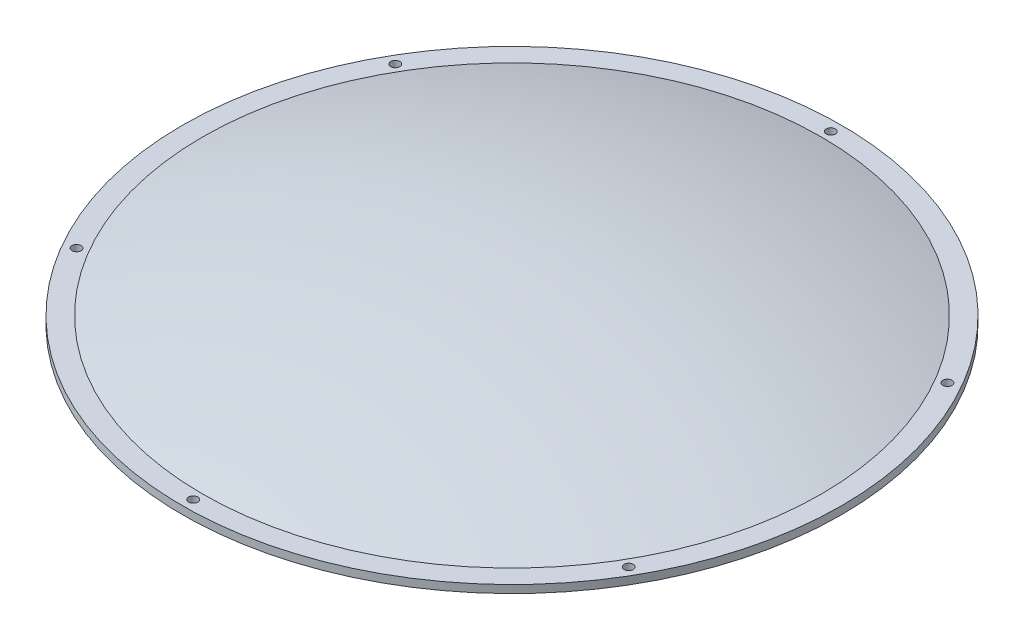
SolidWorks part; units mm, degrees
material "6061-T6 (SS)"
ref_plane "Front Plane" through (0, 0, 0) normal (0, 0, 1) x (1, 0, 0)
ref_plane "Top Plane" through (0, 0, 0) normal (0, 1, 0) x (1, 0, 0)
ref_plane "Right Plane" through (0, 0, 0) normal (1, 0, 0) x (0, 0, -1)
sketch "Sketch1" plane through (0, 0, 0) normal (0, 0, 1) x (1, 0, 0)
  line L0 (-107.3799, 282.8427) -> (107.3799, 282.8427)
  line L1 (0, 282.8427) -> (0, 102.1032)
  line L2 (0, 302.54) -> (0, 300)
  line L3 (100, 282.8427) -> (107, 282.8427)
  line L4 (0, 300) -> (-94.3927, 300) construction
  line L5 (100.4348, 285.3827) -> (107, 285.3827)
  line L6 (107, 282.8427) -> (107, 285.3827)
  line L7 (-100, 282.8427) -> (0, 0) construction
  line L8 (0, 0) -> (100, 282.8427) construction
  arc A0 (107.3799, 282.8427) -> (-107.3799, 282.8427) centre (0, 0) ccw
  arc A1 (100, 282.8427) -> (-100, 282.8427) centre (0, 0) ccw
  circle A2 centre (0, 0) radius 300 construction
  circle A3 centre (0, 0) radius 302.54 construction
  circle A4 centre (0, 0) radius 300 construction
  point P1 (149, 0)
  point P5 (0, 302.54)
  point P8 (143.4457, 43.8558)
  dimension "D1" = 300
  dimension "D2" = 200
  dimension "D4" = 2.54
  dimension "D5" = 107
  dimension "D3" = 2.54
revolve "Revolve1" add sketch "Sketch1" angle 360 about L1 region at (50.7617, 297.1474, 0) region at (104.8248, 284.5888, 0)
sketch "Sketch4" plane through (0, 282.8427, 0) normal (0, -1, 0) x (1, 0, 0)
  circle A0 centre (0, 0) radius 103.5 construction
  circle A1 centre (0, 103.5) radius 1.4732
  circle A2 centre (89.6336, 51.75) radius 1.4732
  circle A3 centre (89.6336, -51.75) radius 1.4732
  circle A4 centre (0, -103.5) radius 1.4732
  circle A5 centre (-89.6336, -51.75) radius 1.4732
  circle A6 centre (-89.6336, 51.75) radius 1.4732
  dimension "D1" = 207
  dimension "D2" = 2.9464
  dimension "D3" = 6
extrude "Cut-Extrude1" cut sketch "Sketch4" against normal through all
ref_plane "Plane1" through (0, 152, 0) normal (0, 1, 0) x (-1, 0, 0)
sketch "Sketch5" plane through (0, 152, 0) normal (0, 1, 0) x (-1, 0, 0)
  line L0 (0.866, 0) -> (2.4628, 0) construction
  line L1 (0.433, -0.75) -> (0.866, 0)
  line L2 (0.866, 0) -> (0.433, 0.75)
  line L3 (0.433, 0.75) -> (-0.433, 0.75)
  line L4 (-0.433, 0.75) -> (-0.866, 0)
  line L5 (-0.866, 0) -> (-0.433, -0.75)
  line L6 (-0.433, -0.75) -> (0.433, -0.75)
  line L7 (2.557, -0.75) -> (3.423, -0.75)
  line L8 (2.363, 0.8643) -> (1.93, 1.6143)
  line L9 (1.93, 1.6143) -> (1.064, 1.6143)
  line L10 (1.064, 1.6143) -> (0.631, 0.8643)
  line L11 (0.631, 0.8643) -> (1.064, 0.1143)
  line L12 (1.064, 0.1143) -> (1.93, 0.1143)
  line L13 (1.93, 0.1143) -> (2.363, 0.8643)
  line L14 (2.124, 0) -> (2.557, -0.75)
  line L15 (2.557, 0.75) -> (2.124, 0)
  line L16 (3.423, 0.75) -> (2.557, 0.75)
  line L17 (3.856, 0) -> (3.423, 0.75)
  line L18 (3.423, -0.75) -> (3.856, 0)
  line L19 (3.621, 0.8643) -> (4.054, 0.1143)
  line L20 (4.054, 1.6143) -> (3.621, 0.8643)
  line L21 (4.92, 1.6143) -> (4.054, 1.6143)
  line L22 (5.353, 0.8643) -> (4.92, 1.6143)
  line L23 (4.92, 0.1143) -> (5.353, 0.8643)
  line L24 (4.054, 0.1143) -> (4.92, 0.1143)
  line L25 (5.547, -0.75) -> (6.413, -0.75)
  line L26 (5.114, 0) -> (5.547, -0.75)
  line L27 (5.547, 0.75) -> (5.114, 0)
  line L28 (6.413, 0.75) -> (5.547, 0.75)
  line L29 (6.846, 0) -> (6.413, 0.75)
  line L30 (6.413, -0.75) -> (6.846, 0)
  line L31 (6.611, 0.8643) -> (7.044, 0.1143)
  line L32 (7.044, 1.6143) -> (6.611, 0.8643)
  line L33 (7.91, 1.6143) -> (7.044, 1.6143)
  line L34 (8.343, 0.8643) -> (7.91, 1.6143)
  line L35 (7.91, 0.1143) -> (8.343, 0.8643)
  line L36 (7.044, 0.1143) -> (7.91, 0.1143)
  line L37 (8.537, -0.75) -> (9.403, -0.75)
  line L38 (8.104, 0) -> (8.537, -0.75)
  line L39 (8.537, 0.75) -> (8.104, 0)
  line L40 (9.403, 0.75) -> (8.537, 0.75)
  line L41 (9.836, 0) -> (9.403, 0.75)
  line L42 (9.403, -0.75) -> (9.836, 0)
  line L43 (9.601, 0.8643) -> (10.034, 0.1143)
  line L44 (10.034, 1.6143) -> (9.601, 0.8643)
  line L45 (10.9, 1.6143) -> (10.034, 1.6143)
  line L46 (11.333, 0.8643) -> (10.9, 1.6143)
  line L47 (10.9, 0.1143) -> (11.333, 0.8643)
  line L48 (10.034, 0.1143) -> (10.9, 0.1143)
  line L49 (11.527, -0.75) -> (12.393, -0.75)
  line L50 (11.094, 0) -> (11.527, -0.75)
  line L51 (11.527, 0.75) -> (11.094, 0)
  line L52 (12.393, 0.75) -> (11.527, 0.75)
  line L53 (12.826, 0) -> (12.393, 0.75)
  line L54 (12.393, -0.75) -> (12.826, 0)
  line L55 (12.591, 0.8643) -> (13.024, 0.1143)
  line L56 (13.024, 1.6143) -> (12.591, 0.8643)
  line L57 (13.89, 1.6143) -> (13.024, 1.6143)
  line L58 (14.323, 0.8643) -> (13.89, 1.6143)
  line L59 (13.89, 0.1143) -> (14.323, 0.8643)
  line L60 (13.024, 0.1143) -> (13.89, 0.1143)
  line L61 (14.517, -0.75) -> (15.383, -0.75)
  line L62 (14.084, 0) -> (14.517, -0.75)
  line L63 (14.517, 0.75) -> (14.084, 0)
  line L64 (15.383, 0.75) -> (14.517, 0.75)
  line L65 (15.816, 0) -> (15.383, 0.75)
  line L66 (15.383, -0.75) -> (15.816, 0)
  line L67 (15.581, 0.8643) -> (16.014, 0.1143)
  line L68 (16.014, 1.6143) -> (15.581, 0.8643)
  line L69 (16.88, 1.6143) -> (16.014, 1.6143)
  line L70 (17.313, 0.8643) -> (16.88, 1.6143)
  line L71 (16.88, 0.1143) -> (17.313, 0.8643)
  line L72 (16.014, 0.1143) -> (16.88, 0.1143)
  line L73 (17.507, -0.75) -> (18.373, -0.75)
  line L74 (17.074, 0) -> (17.507, -0.75)
  line L75 (17.507, 0.75) -> (17.074, 0)
  line L76 (18.373, 0.75) -> (17.507, 0.75)
  line L77 (18.806, 0) -> (18.373, 0.75)
  line L78 (18.373, -0.75) -> (18.806, 0)
  line L79 (18.571, 0.8643) -> (19.004, 0.1143)
  line L80 (19.004, 1.6143) -> (18.571, 0.8643)
  line L81 (19.87, 1.6143) -> (19.004, 1.6143)
  line L82 (20.303, 0.8643) -> (19.87, 1.6143)
  line L83 (19.87, 0.1143) -> (20.303, 0.8643)
  line L84 (19.004, 0.1143) -> (19.87, 0.1143)
  line L85 (20.497, -0.75) -> (21.363, -0.75)
  line L86 (20.064, 0) -> (20.497, -0.75)
  line L87 (20.497, 0.75) -> (20.064, 0)
  line L88 (21.363, 0.75) -> (20.497, 0.75)
  line L89 (21.796, 0) -> (21.363, 0.75)
  line L90 (21.363, -0.75) -> (21.796, 0)
  line L91 (21.561, 0.8643) -> (21.994, 0.1143)
  line L92 (21.994, 1.6143) -> (21.561, 0.8643)
  line L93 (22.86, 1.6143) -> (21.994, 1.6143)
  line L94 (23.293, 0.8643) -> (22.86, 1.6143)
  line L95 (22.86, 0.1143) -> (23.293, 0.8643)
  line L96 (21.994, 0.1143) -> (22.86, 0.1143)
  line L97 (23.487, -0.75) -> (24.353, -0.75)
  line L98 (23.054, 0) -> (23.487, -0.75)
  line L99 (23.487, 0.75) -> (23.054, 0)
  line L100 (24.353, 0.75) -> (23.487, 0.75)
  line L101 (24.786, 0) -> (24.353, 0.75)
  line L102 (24.353, -0.75) -> (24.786, 0)
  line L103 (24.551, 0.8643) -> (24.984, 0.1143)
  line L104 (24.984, 1.6143) -> (24.551, 0.8643)
  line L105 (25.85, 1.6143) -> (24.984, 1.6143)
  line L106 (26.283, 0.8643) -> (25.85, 1.6143)
  line L107 (25.85, 0.1143) -> (26.283, 0.8643)
  line L108 (24.984, 0.1143) -> (25.85, 0.1143)
  line L109 (26.477, -0.75) -> (27.343, -0.75)
  line L110 (26.044, 0) -> (26.477, -0.75)
  line L111 (26.477, 0.75) -> (26.044, 0)
  line L112 (27.343, 0.75) -> (26.477, 0.75)
  line L113 (27.776, 0) -> (27.343, 0.75)
  line L114 (27.343, -0.75) -> (27.776, 0)
  line L115 (27.541, 0.8643) -> (27.974, 0.1143)
  line L116 (27.974, 1.6143) -> (27.541, 0.8643)
  line L117 (28.84, 1.6143) -> (27.974, 1.6143)
  line L118 (29.273, 0.8643) -> (28.84, 1.6143)
  line L119 (28.84, 0.1143) -> (29.273, 0.8643)
  line L120 (27.974, 0.1143) -> (28.84, 0.1143)
  line L121 (-0.433, 0.98) -> (0.433, 0.98)
  line L122 (-0.866, 1.73) -> (-0.433, 0.98)
  line L123 (-0.433, 2.48) -> (-0.866, 1.73)
  line L124 (0.433, 2.48) -> (-0.433, 2.48)
  line L125 (0.866, 1.73) -> (0.433, 2.48)
  line L126 (0.433, 0.98) -> (0.866, 1.73)
  line L127 (0.631, 2.5943) -> (1.064, 1.8443)
  line L128 (1.064, 3.3443) -> (0.631, 2.5943)
  line L129 (1.93, 3.3443) -> (1.064, 3.3443)
  line L130 (2.363, 2.5943) -> (1.93, 3.3443)
  line L131 (1.93, 1.8443) -> (2.363, 2.5943)
  line L132 (1.064, 1.8443) -> (1.93, 1.8443)
  line L133 (2.557, 0.98) -> (3.423, 0.98)
  line L134 (2.124, 1.73) -> (2.557, 0.98)
  line L135 (2.557, 2.48) -> (2.124, 1.73)
  line L136 (3.423, 2.48) -> (2.557, 2.48)
  line L137 (3.856, 1.73) -> (3.423, 2.48)
  line L138 (3.423, 0.98) -> (3.856, 1.73)
  line L139 (3.621, 2.5943) -> (4.054, 1.8443)
  line L140 (4.054, 3.3443) -> (3.621, 2.5943)
  line L141 (4.92, 3.3443) -> (4.054, 3.3443)
  line L142 (5.353, 2.5943) -> (4.92, 3.3443)
  line L143 (4.92, 1.8443) -> (5.353, 2.5943)
  line L144 (4.054, 1.8443) -> (4.92, 1.8443)
  line L145 (5.547, 0.98) -> (6.413, 0.98)
  line L146 (5.114, 1.73) -> (5.547, 0.98)
  line L147 (5.547, 2.48) -> (5.114, 1.73)
  line L148 (6.413, 2.48) -> (5.547, 2.48)
  line L149 (6.846, 1.73) -> (6.413, 2.48)
  line L150 (6.413, 0.98) -> (6.846, 1.73)
  line L151 (6.611, 2.5943) -> (7.044, 1.8443)
  line L152 (7.044, 3.3443) -> (6.611, 2.5943)
  line L153 (7.91, 3.3443) -> (7.044, 3.3443)
  line L154 (8.343, 2.5943) -> (7.91, 3.3443)
  line L155 (7.91, 1.8443) -> (8.343, 2.5943)
  line L156 (7.044, 1.8443) -> (7.91, 1.8443)
  line L157 (8.537, 0.98) -> (9.403, 0.98)
  line L158 (8.104, 1.73) -> (8.537, 0.98)
  line L159 (8.537, 2.48) -> (8.104, 1.73)
  line L160 (9.403, 2.48) -> (8.537, 2.48)
  line L161 (9.836, 1.73) -> (9.403, 2.48)
  line L162 (9.403, 0.98) -> (9.836, 1.73)
  line L163 (9.601, 2.5943) -> (10.034, 1.8443)
  line L164 (10.034, 3.3443) -> (9.601, 2.5943)
  line L165 (10.9, 3.3443) -> (10.034, 3.3443)
  line L166 (11.333, 2.5943) -> (10.9, 3.3443)
  line L167 (10.9, 1.8443) -> (11.333, 2.5943)
  line L168 (10.034, 1.8443) -> (10.9, 1.8443)
  line L169 (11.527, 0.98) -> (12.393, 0.98)
  line L170 (11.094, 1.73) -> (11.527, 0.98)
  line L171 (11.527, 2.48) -> (11.094, 1.73)
  line L172 (12.393, 2.48) -> (11.527, 2.48)
  line L173 (12.826, 1.73) -> (12.393, 2.48)
  line L174 (12.393, 0.98) -> (12.826, 1.73)
  line L175 (12.591, 2.5943) -> (13.024, 1.8443)
  line L176 (13.024, 3.3443) -> (12.591, 2.5943)
  line L177 (13.89, 3.3443) -> (13.024, 3.3443)
  line L178 (14.323, 2.5943) -> (13.89, 3.3443)
  line L179 (13.89, 1.8443) -> (14.323, 2.5943)
  line L180 (13.024, 1.8443) -> (13.89, 1.8443)
  line L181 (14.517, 0.98) -> (15.383, 0.98)
  line L182 (14.084, 1.73) -> (14.517, 0.98)
  line L183 (14.517, 2.48) -> (14.084, 1.73)
  line L184 (15.383, 2.48) -> (14.517, 2.48)
  line L185 (15.816, 1.73) -> (15.383, 2.48)
  line L186 (15.383, 0.98) -> (15.816, 1.73)
  line L187 (15.581, 2.5943) -> (16.014, 1.8443)
  line L188 (16.014, 3.3443) -> (15.581, 2.5943)
  line L189 (16.88, 3.3443) -> (16.014, 3.3443)
  line L190 (17.313, 2.5943) -> (16.88, 3.3443)
  line L191 (16.88, 1.8443) -> (17.313, 2.5943)
  line L192 (16.014, 1.8443) -> (16.88, 1.8443)
  line L193 (17.507, 0.98) -> (18.373, 0.98)
  line L194 (17.074, 1.73) -> (17.507, 0.98)
  line L195 (17.507, 2.48) -> (17.074, 1.73)
  line L196 (18.373, 2.48) -> (17.507, 2.48)
  line L197 (18.806, 1.73) -> (18.373, 2.48)
  line L198 (18.373, 0.98) -> (18.806, 1.73)
  line L199 (18.571, 2.5943) -> (19.004, 1.8443)
  line L200 (19.004, 3.3443) -> (18.571, 2.5943)
  line L201 (19.87, 3.3443) -> (19.004, 3.3443)
  line L202 (20.303, 2.5943) -> (19.87, 3.3443)
  line L203 (19.87, 1.8443) -> (20.303, 2.5943)
  line L204 (19.004, 1.8443) -> (19.87, 1.8443)
  line L205 (20.497, 0.98) -> (21.363, 0.98)
  line L206 (20.064, 1.73) -> (20.497, 0.98)
  line L207 (20.497, 2.48) -> (20.064, 1.73)
  line L208 (21.363, 2.48) -> (20.497, 2.48)
  line L209 (21.796, 1.73) -> (21.363, 2.48)
  line L210 (21.363, 0.98) -> (21.796, 1.73)
  line L211 (21.561, 2.5943) -> (21.994, 1.8443)
  line L212 (21.994, 3.3443) -> (21.561, 2.5943)
  line L213 (22.86, 3.3443) -> (21.994, 3.3443)
  line L214 (23.293, 2.5943) -> (22.86, 3.3443)
  line L215 (22.86, 1.8443) -> (23.293, 2.5943)
  line L216 (21.994, 1.8443) -> (22.86, 1.8443)
  line L217 (23.487, 0.98) -> (24.353, 0.98)
  line L218 (23.054, 1.73) -> (23.487, 0.98)
  line L219 (23.487, 2.48) -> (23.054, 1.73)
  line L220 (24.353, 2.48) -> (23.487, 2.48)
  line L221 (24.786, 1.73) -> (24.353, 2.48)
  line L222 (24.353, 0.98) -> (24.786, 1.73)
  line L223 (24.551, 2.5943) -> (24.984, 1.8443)
  line L224 (24.984, 3.3443) -> (24.551, 2.5943)
  line L225 (25.85, 3.3443) -> (24.984, 3.3443)
  line L226 (26.283, 2.5943) -> (25.85, 3.3443)
  line L227 (25.85, 1.8443) -> (26.283, 2.5943)
  line L228 (24.984, 1.8443) -> (25.85, 1.8443)
  line L229 (26.477, 0.98) -> (27.343, 0.98)
  line L230 (26.044, 1.73) -> (26.477, 0.98)
  line L231 (26.477, 2.48) -> (26.044, 1.73)
  line L232 (27.343, 2.48) -> (26.477, 2.48)
  line L233 (27.776, 1.73) -> (27.343, 2.48)
  line L234 (27.343, 0.98) -> (27.776, 1.73)
  line L235 (27.541, 2.5943) -> (27.974, 1.8443)
  line L236 (27.974, 3.3443) -> (27.541, 2.5943)
  line L237 (28.84, 3.3443) -> (27.974, 3.3443)
  line L238 (29.273, 2.5943) -> (28.84, 3.3443)
  line L239 (28.84, 1.8443) -> (29.273, 2.5943)
  line L240 (27.974, 1.8443) -> (28.84, 1.8443)
  line L241 (-0.433, 2.71) -> (0.433, 2.71)
  line L242 (-0.866, 3.46) -> (-0.433, 2.71)
  line L243 (-0.433, 4.21) -> (-0.866, 3.46)
  line L244 (0.433, 4.21) -> (-0.433, 4.21)
  line L245 (0.866, 3.46) -> (0.433, 4.21)
  line L246 (0.433, 2.71) -> (0.866, 3.46)
  line L247 (0.631, 4.3243) -> (1.064, 3.5743)
  line L248 (1.064, 5.0743) -> (0.631, 4.3243)
  line L249 (1.93, 5.0743) -> (1.064, 5.0743)
  line L250 (2.363, 4.3243) -> (1.93, 5.0743)
  line L251 (1.93, 3.5743) -> (2.363, 4.3243)
  line L252 (1.064, 3.5743) -> (1.93, 3.5743)
  line L253 (2.557, 2.71) -> (3.423, 2.71)
  line L254 (2.124, 3.46) -> (2.557, 2.71)
  line L255 (2.557, 4.21) -> (2.124, 3.46)
  line L256 (3.423, 4.21) -> (2.557, 4.21)
  line L257 (3.856, 3.46) -> (3.423, 4.21)
  line L258 (3.423, 2.71) -> (3.856, 3.46)
  line L259 (3.621, 4.3243) -> (4.054, 3.5743)
  line L260 (4.054, 5.0743) -> (3.621, 4.3243)
  line L261 (4.92, 5.0743) -> (4.054, 5.0743)
  line L262 (5.353, 4.3243) -> (4.92, 5.0743)
  line L263 (4.92, 3.5743) -> (5.353, 4.3243)
  line L264 (4.054, 3.5743) -> (4.92, 3.5743)
  line L265 (5.547, 2.71) -> (6.413, 2.71)
  line L266 (5.114, 3.46) -> (5.547, 2.71)
  line L267 (5.547, 4.21) -> (5.114, 3.46)
  line L268 (6.413, 4.21) -> (5.547, 4.21)
  line L269 (6.846, 3.46) -> (6.413, 4.21)
  line L270 (6.413, 2.71) -> (6.846, 3.46)
  line L271 (6.611, 4.3243) -> (7.044, 3.5743)
  line L272 (7.044, 5.0743) -> (6.611, 4.3243)
  line L273 (7.91, 5.0743) -> (7.044, 5.0743)
  line L274 (8.343, 4.3243) -> (7.91, 5.0743)
  line L275 (7.91, 3.5743) -> (8.343, 4.3243)
  line L276 (7.044, 3.5743) -> (7.91, 3.5743)
  line L277 (8.537, 2.71) -> (9.403, 2.71)
  line L278 (8.104, 3.46) -> (8.537, 2.71)
  line L279 (8.537, 4.21) -> (8.104, 3.46)
  line L280 (9.403, 4.21) -> (8.537, 4.21)
  line L281 (9.836, 3.46) -> (9.403, 4.21)
  line L282 (9.403, 2.71) -> (9.836, 3.46)
  line L283 (9.601, 4.3243) -> (10.034, 3.5743)
  line L284 (10.034, 5.0743) -> (9.601, 4.3243)
  line L285 (10.9, 5.0743) -> (10.034, 5.0743)
  line L286 (11.333, 4.3243) -> (10.9, 5.0743)
  line L287 (10.9, 3.5743) -> (11.333, 4.3243)
  line L288 (10.034, 3.5743) -> (10.9, 3.5743)
  line L289 (11.527, 2.71) -> (12.393, 2.71)
  line L290 (11.094, 3.46) -> (11.527, 2.71)
  line L291 (11.527, 4.21) -> (11.094, 3.46)
  line L292 (12.393, 4.21) -> (11.527, 4.21)
  line L293 (12.826, 3.46) -> (12.393, 4.21)
  line L294 (12.393, 2.71) -> (12.826, 3.46)
  line L295 (12.591, 4.3243) -> (13.024, 3.5743)
  line L296 (13.024, 5.0743) -> (12.591, 4.3243)
  line L297 (13.89, 5.0743) -> (13.024, 5.0743)
  line L298 (14.323, 4.3243) -> (13.89, 5.0743)
  line L299 (13.89, 3.5743) -> (14.323, 4.3243)
  line L300 (13.024, 3.5743) -> (13.89, 3.5743)
  line L301 (14.517, 2.71) -> (15.383, 2.71)
  line L302 (14.084, 3.46) -> (14.517, 2.71)
  line L303 (14.517, 4.21) -> (14.084, 3.46)
  line L304 (15.383, 4.21) -> (14.517, 4.21)
  line L305 (15.816, 3.46) -> (15.383, 4.21)
  line L306 (15.383, 2.71) -> (15.816, 3.46)
  line L307 (15.581, 4.3243) -> (16.014, 3.5743)
  line L308 (16.014, 5.0743) -> (15.581, 4.3243)
  line L309 (16.88, 5.0743) -> (16.014, 5.0743)
  line L310 (17.313, 4.3243) -> (16.88, 5.0743)
  line L311 (16.88, 3.5743) -> (17.313, 4.3243)
  line L312 (16.014, 3.5743) -> (16.88, 3.5743)
  line L313 (17.507, 2.71) -> (18.373, 2.71)
  line L314 (17.074, 3.46) -> (17.507, 2.71)
  line L315 (17.507, 4.21) -> (17.074, 3.46)
  line L316 (18.373, 4.21) -> (17.507, 4.21)
  line L317 (18.806, 3.46) -> (18.373, 4.21)
  line L318 (18.373, 2.71) -> (18.806, 3.46)
  line L319 (18.571, 4.3243) -> (19.004, 3.5743)
  line L320 (19.004, 5.0743) -> (18.571, 4.3243)
  line L321 (19.87, 5.0743) -> (19.004, 5.0743)
  line L322 (20.303, 4.3243) -> (19.87, 5.0743)
  line L323 (19.87, 3.5743) -> (20.303, 4.3243)
  line L324 (19.004, 3.5743) -> (19.87, 3.5743)
  line L325 (20.497, 2.71) -> (21.363, 2.71)
  line L326 (20.064, 3.46) -> (20.497, 2.71)
  line L327 (20.497, 4.21) -> (20.064, 3.46)
  line L328 (21.363, 4.21) -> (20.497, 4.21)
  line L329 (21.796, 3.46) -> (21.363, 4.21)
  line L330 (21.363, 2.71) -> (21.796, 3.46)
  line L331 (21.561, 4.3243) -> (21.994, 3.5743)
  line L332 (21.994, 5.0743) -> (21.561, 4.3243)
  line L333 (22.86, 5.0743) -> (21.994, 5.0743)
  line L334 (23.293, 4.3243) -> (22.86, 5.0743)
  line L335 (22.86, 3.5743) -> (23.293, 4.3243)
  line L336 (21.994, 3.5743) -> (22.86, 3.5743)
  line L337 (23.487, 2.71) -> (24.353, 2.71)
  line L338 (23.054, 3.46) -> (23.487, 2.71)
  line L339 (23.487, 4.21) -> (23.054, 3.46)
  line L340 (24.353, 4.21) -> (23.487, 4.21)
  line L341 (24.786, 3.46) -> (24.353, 4.21)
  line L342 (24.353, 2.71) -> (24.786, 3.46)
  line L343 (24.551, 4.3243) -> (24.984, 3.5743)
  line L344 (24.984, 5.0743) -> (24.551, 4.3243)
  line L345 (25.85, 5.0743) -> (24.984, 5.0743)
  line L346 (26.283, 4.3243) -> (25.85, 5.0743)
  line L347 (25.85, 3.5743) -> (26.283, 4.3243)
  line L348 (24.984, 3.5743) -> (25.85, 3.5743)
  line L349 (26.477, 2.71) -> (27.343, 2.71)
  line L350 (26.044, 3.46) -> (26.477, 2.71)
  line L351 (26.477, 4.21) -> (26.044, 3.46)
  line L352 (27.343, 4.21) -> (26.477, 4.21)
  line L353 (27.776, 3.46) -> (27.343, 4.21)
  line L354 (27.343, 2.71) -> (27.776, 3.46)
  line L355 (27.541, 4.3243) -> (27.974, 3.5743)
  line L356 (27.974, 5.0743) -> (27.541, 4.3243)
  line L357 (28.84, 5.0743) -> (27.974, 5.0743)
  line L358 (29.273, 4.3243) -> (28.84, 5.0743)
  line L359 (28.84, 3.5743) -> (29.273, 4.3243)
  line L360 (27.974, 3.5743) -> (28.84, 3.5743)
  line L361 (-0.433, 4.44) -> (0.433, 4.44)
  line L362 (-0.866, 5.19) -> (-0.433, 4.44)
  line L363 (-0.433, 5.94) -> (-0.866, 5.19)
  line L364 (0.433, 5.94) -> (-0.433, 5.94)
  line L365 (0.866, 5.19) -> (0.433, 5.94)
  line L366 (0.433, 4.44) -> (0.866, 5.19)
  line L367 (0.631, 6.0543) -> (1.064, 5.3043)
  line L368 (1.064, 6.8043) -> (0.631, 6.0543)
  line L369 (1.93, 6.8043) -> (1.064, 6.8043)
  line L370 (2.363, 6.0543) -> (1.93, 6.8043)
  line L371 (1.93, 5.3043) -> (2.363, 6.0543)
  line L372 (1.064, 5.3043) -> (1.93, 5.3043)
  line L373 (2.557, 4.44) -> (3.423, 4.44)
  line L374 (2.124, 5.19) -> (2.557, 4.44)
  line L375 (2.557, 5.94) -> (2.124, 5.19)
  line L376 (3.423, 5.94) -> (2.557, 5.94)
  line L377 (3.856, 5.19) -> (3.423, 5.94)
  line L378 (3.423, 4.44) -> (3.856, 5.19)
  line L379 (3.621, 6.0543) -> (4.054, 5.3043)
  line L380 (4.054, 6.8043) -> (3.621, 6.0543)
  line L381 (4.92, 6.8043) -> (4.054, 6.8043)
  line L382 (5.353, 6.0543) -> (4.92, 6.8043)
  line L383 (4.92, 5.3043) -> (5.353, 6.0543)
  line L384 (4.054, 5.3043) -> (4.92, 5.3043)
  line L385 (5.547, 4.44) -> (6.413, 4.44)
  line L386 (5.114, 5.19) -> (5.547, 4.44)
  line L387 (5.547, 5.94) -> (5.114, 5.19)
  line L388 (6.413, 5.94) -> (5.547, 5.94)
  line L389 (6.846, 5.19) -> (6.413, 5.94)
  line L390 (6.413, 4.44) -> (6.846, 5.19)
  line L391 (6.611, 6.0543) -> (7.044, 5.3043)
  line L392 (7.044, 6.8043) -> (6.611, 6.0543)
  line L393 (7.91, 6.8043) -> (7.044, 6.8043)
  line L394 (8.343, 6.0543) -> (7.91, 6.8043)
  line L395 (7.91, 5.3043) -> (8.343, 6.0543)
  line L396 (7.044, 5.3043) -> (7.91, 5.3043)
  line L397 (8.537, 4.44) -> (9.403, 4.44)
  line L398 (8.104, 5.19) -> (8.537, 4.44)
  line L399 (8.537, 5.94) -> (8.104, 5.19)
  line L400 (9.403, 5.94) -> (8.537, 5.94)
  line L401 (9.836, 5.19) -> (9.403, 5.94)
  line L402 (9.403, 4.44) -> (9.836, 5.19)
  line L403 (9.601, 6.0543) -> (10.034, 5.3043)
  line L404 (10.034, 6.8043) -> (9.601, 6.0543)
  line L405 (10.9, 6.8043) -> (10.034, 6.8043)
  line L406 (11.333, 6.0543) -> (10.9, 6.8043)
  line L407 (10.9, 5.3043) -> (11.333, 6.0543)
  line L408 (10.034, 5.3043) -> (10.9, 5.3043)
  line L409 (11.527, 4.44) -> (12.393, 4.44)
  line L410 (11.094, 5.19) -> (11.527, 4.44)
  line L411 (11.527, 5.94) -> (11.094, 5.19)
  line L412 (12.393, 5.94) -> (11.527, 5.94)
  line L413 (12.826, 5.19) -> (12.393, 5.94)
  line L414 (12.393, 4.44) -> (12.826, 5.19)
  line L415 (12.591, 6.0543) -> (13.024, 5.3043)
  line L416 (13.024, 6.8043) -> (12.591, 6.0543)
  line L417 (13.89, 6.8043) -> (13.024, 6.8043)
  line L418 (14.323, 6.0543) -> (13.89, 6.8043)
  line L419 (13.89, 5.3043) -> (14.323, 6.0543)
  line L420 (13.024, 5.3043) -> (13.89, 5.3043)
  line L421 (14.517, 4.44) -> (15.383, 4.44)
  line L422 (14.084, 5.19) -> (14.517, 4.44)
  line L423 (14.517, 5.94) -> (14.084, 5.19)
  line L424 (15.383, 5.94) -> (14.517, 5.94)
  line L425 (15.816, 5.19) -> (15.383, 5.94)
  line L426 (15.383, 4.44) -> (15.816, 5.19)
  line L427 (15.581, 6.0543) -> (16.014, 5.3043)
  line L428 (16.014, 6.8043) -> (15.581, 6.0543)
  line L429 (16.88, 6.8043) -> (16.014, 6.8043)
  line L430 (17.313, 6.0543) -> (16.88, 6.8043)
  line L431 (16.88, 5.3043) -> (17.313, 6.0543)
  line L432 (16.014, 5.3043) -> (16.88, 5.3043)
  line L433 (17.507, 4.44) -> (18.373, 4.44)
  line L434 (17.074, 5.19) -> (17.507, 4.44)
  line L435 (17.507, 5.94) -> (17.074, 5.19)
  line L436 (18.373, 5.94) -> (17.507, 5.94)
  line L437 (18.806, 5.19) -> (18.373, 5.94)
  line L438 (18.373, 4.44) -> (18.806, 5.19)
  line L439 (18.571, 6.0543) -> (19.004, 5.3043)
  line L440 (19.004, 6.8043) -> (18.571, 6.0543)
  line L441 (19.87, 6.8043) -> (19.004, 6.8043)
  line L442 (20.303, 6.0543) -> (19.87, 6.8043)
  line L443 (19.87, 5.3043) -> (20.303, 6.0543)
  line L444 (19.004, 5.3043) -> (19.87, 5.3043)
  line L445 (20.497, 4.44) -> (21.363, 4.44)
  line L446 (20.064, 5.19) -> (20.497, 4.44)
  line L447 (20.497, 5.94) -> (20.064, 5.19)
  line L448 (21.363, 5.94) -> (20.497, 5.94)
  line L449 (21.796, 5.19) -> (21.363, 5.94)
  line L450 (21.363, 4.44) -> (21.796, 5.19)
  line L451 (21.561, 6.0543) -> (21.994, 5.3043)
  line L452 (21.994, 6.8043) -> (21.561, 6.0543)
  line L453 (22.86, 6.8043) -> (21.994, 6.8043)
  line L454 (23.293, 6.0543) -> (22.86, 6.8043)
  line L455 (22.86, 5.3043) -> (23.293, 6.0543)
  line L456 (21.994, 5.3043) -> (22.86, 5.3043)
  line L457 (23.487, 4.44) -> (24.353, 4.44)
  line L458 (23.054, 5.19) -> (23.487, 4.44)
  line L459 (23.487, 5.94) -> (23.054, 5.19)
  line L460 (24.353, 5.94) -> (23.487, 5.94)
  line L461 (24.786, 5.19) -> (24.353, 5.94)
  line L462 (24.353, 4.44) -> (24.786, 5.19)
  line L463 (24.551, 6.0543) -> (24.984, 5.3043)
  line L464 (24.984, 6.8043) -> (24.551, 6.0543)
  line L465 (25.85, 6.8043) -> (24.984, 6.8043)
  line L466 (26.283, 6.0543) -> (25.85, 6.8043)
  line L467 (25.85, 5.3043) -> (26.283, 6.0543)
  line L468 (24.984, 5.3043) -> (25.85, 5.3043)
  line L469 (26.477, 4.44) -> (27.343, 4.44)
  line L470 (26.044, 5.19) -> (26.477, 4.44)
  line L471 (26.477, 5.94) -> (26.044, 5.19)
  line L472 (27.343, 5.94) -> (26.477, 5.94)
  line L473 (27.776, 5.19) -> (27.343, 5.94)
  line L474 (27.343, 4.44) -> (27.776, 5.19)
  line L475 (27.541, 6.0543) -> (27.974, 5.3043)
  line L476 (27.974, 6.8043) -> (27.541, 6.0543)
  line L477 (28.84, 6.8043) -> (27.974, 6.8043)
  line L478 (29.273, 6.0543) -> (28.84, 6.8043)
  line L479 (28.84, 5.3043) -> (29.273, 6.0543)
  line L480 (27.974, 5.3043) -> (28.84, 5.3043)
  line L481 (-0.433, 6.17) -> (0.433, 6.17)
  line L482 (-0.866, 6.92) -> (-0.433, 6.17)
  line L483 (-0.433, 7.67) -> (-0.866, 6.92)
  line L484 (0.433, 7.67) -> (-0.433, 7.67)
  line L485 (0.866, 6.92) -> (0.433, 7.67)
  line L486 (0.433, 6.17) -> (0.866, 6.92)
  line L487 (0.631, 7.7843) -> (1.064, 7.0343)
  line L488 (1.064, 8.5343) -> (0.631, 7.7843)
  line L489 (1.93, 8.5343) -> (1.064, 8.5343)
  line L490 (2.363, 7.7843) -> (1.93, 8.5343)
  line L491 (1.93, 7.0343) -> (2.363, 7.7843)
  line L492 (1.064, 7.0343) -> (1.93, 7.0343)
  line L493 (2.557, 6.17) -> (3.423, 6.17)
  line L494 (2.124, 6.92) -> (2.557, 6.17)
  line L495 (2.557, 7.67) -> (2.124, 6.92)
  line L496 (3.423, 7.67) -> (2.557, 7.67)
  line L497 (3.856, 6.92) -> (3.423, 7.67)
  line L498 (3.423, 6.17) -> (3.856, 6.92)
  line L499 (3.621, 7.7843) -> (4.054, 7.0343)
  line L500 (4.054, 8.5343) -> (3.621, 7.7843)
  line L501 (4.92, 8.5343) -> (4.054, 8.5343)
  line L502 (5.353, 7.7843) -> (4.92, 8.5343)
  line L503 (4.92, 7.0343) -> (5.353, 7.7843)
  line L504 (4.054, 7.0343) -> (4.92, 7.0343)
  line L505 (5.547, 6.17) -> (6.413, 6.17)
  line L506 (5.114, 6.92) -> (5.547, 6.17)
  line L507 (5.547, 7.67) -> (5.114, 6.92)
  line L508 (6.413, 7.67) -> (5.547, 7.67)
  line L509 (6.846, 6.92) -> (6.413, 7.67)
  line L510 (6.413, 6.17) -> (6.846, 6.92)
  line L511 (6.611, 7.7843) -> (7.044, 7.0343)
  line L512 (7.044, 8.5343) -> (6.611, 7.7843)
  line L513 (7.91, 8.5343) -> (7.044, 8.5343)
  line L514 (8.343, 7.7843) -> (7.91, 8.5343)
  line L515 (7.91, 7.0343) -> (8.343, 7.7843)
  line L516 (7.044, 7.0343) -> (7.91, 7.0343)
  line L517 (8.537, 6.17) -> (9.403, 6.17)
  line L518 (8.104, 6.92) -> (8.537, 6.17)
  line L519 (8.537, 7.67) -> (8.104, 6.92)
  line L520 (9.403, 7.67) -> (8.537, 7.67)
  line L521 (9.836, 6.92) -> (9.403, 7.67)
  line L522 (9.403, 6.17) -> (9.836, 6.92)
  line L523 (9.601, 7.7843) -> (10.034, 7.0343)
  line L524 (10.034, 8.5343) -> (9.601, 7.7843)
  line L525 (10.9, 8.5343) -> (10.034, 8.5343)
  line L526 (11.333, 7.7843) -> (10.9, 8.5343)
  line L527 (10.9, 7.0343) -> (11.333, 7.7843)
  line L528 (10.034, 7.0343) -> (10.9, 7.0343)
  line L529 (11.527, 6.17) -> (12.393, 6.17)
  line L530 (11.094, 6.92) -> (11.527, 6.17)
  line L531 (11.527, 7.67) -> (11.094, 6.92)
  line L532 (12.393, 7.67) -> (11.527, 7.67)
  line L533 (12.826, 6.92) -> (12.393, 7.67)
  line L534 (12.393, 6.17) -> (12.826, 6.92)
  line L535 (12.591, 7.7843) -> (13.024, 7.0343)
  line L536 (13.024, 8.5343) -> (12.591, 7.7843)
  line L537 (13.89, 8.5343) -> (13.024, 8.5343)
  line L538 (14.323, 7.7843) -> (13.89, 8.5343)
  line L539 (13.89, 7.0343) -> (14.323, 7.7843)
  line L540 (13.024, 7.0343) -> (13.89, 7.0343)
  line L541 (14.517, 6.17) -> (15.383, 6.17)
  line L542 (14.084, 6.92) -> (14.517, 6.17)
  line L543 (14.517, 7.67) -> (14.084, 6.92)
  line L544 (15.383, 7.67) -> (14.517, 7.67)
  line L545 (15.816, 6.92) -> (15.383, 7.67)
  line L546 (15.383, 6.17) -> (15.816, 6.92)
  line L547 (15.581, 7.7843) -> (16.014, 7.0343)
  line L548 (16.014, 8.5343) -> (15.581, 7.7843)
  line L549 (16.88, 8.5343) -> (16.014, 8.5343)
  line L550 (17.313, 7.7843) -> (16.88, 8.5343)
  line L551 (16.88, 7.0343) -> (17.313, 7.7843)
  line L552 (16.014, 7.0343) -> (16.88, 7.0343)
  line L553 (17.507, 6.17) -> (18.373, 6.17)
  line L554 (17.074, 6.92) -> (17.507, 6.17)
  line L555 (17.507, 7.67) -> (17.074, 6.92)
  line L556 (18.373, 7.67) -> (17.507, 7.67)
  line L557 (18.806, 6.92) -> (18.373, 7.67)
  line L558 (18.373, 6.17) -> (18.806, 6.92)
  line L559 (18.571, 7.7843) -> (19.004, 7.0343)
  line L560 (19.004, 8.5343) -> (18.571, 7.7843)
  line L561 (19.87, 8.5343) -> (19.004, 8.5343)
  line L562 (20.303, 7.7843) -> (19.87, 8.5343)
  line L563 (19.87, 7.0343) -> (20.303, 7.7843)
  line L564 (19.004, 7.0343) -> (19.87, 7.0343)
  line L565 (20.497, 6.17) -> (21.363, 6.17)
  line L566 (20.064, 6.92) -> (20.497, 6.17)
  line L567 (20.497, 7.67) -> (20.064, 6.92)
  line L568 (21.363, 7.67) -> (20.497, 7.67)
  line L569 (21.796, 6.92) -> (21.363, 7.67)
  line L570 (21.363, 6.17) -> (21.796, 6.92)
  line L571 (21.561, 7.7843) -> (21.994, 7.0343)
  line L572 (21.994, 8.5343) -> (21.561, 7.7843)
  line L573 (22.86, 8.5343) -> (21.994, 8.5343)
  line L574 (23.293, 7.7843) -> (22.86, 8.5343)
  line L575 (22.86, 7.0343) -> (23.293, 7.7843)
  line L576 (21.994, 7.0343) -> (22.86, 7.0343)
  line L577 (23.487, 6.17) -> (24.353, 6.17)
  line L578 (23.054, 6.92) -> (23.487, 6.17)
  line L579 (23.487, 7.67) -> (23.054, 6.92)
  line L580 (24.353, 7.67) -> (23.487, 7.67)
  line L581 (24.786, 6.92) -> (24.353, 7.67)
  line L582 (24.353, 6.17) -> (24.786, 6.92)
  line L583 (24.551, 7.7843) -> (24.984, 7.0343)
  line L584 (24.984, 8.5343) -> (24.551, 7.7843)
  line L585 (25.85, 8.5343) -> (24.984, 8.5343)
  line L586 (26.283, 7.7843) -> (25.85, 8.5343)
  line L587 (25.85, 7.0343) -> (26.283, 7.7843)
  line L588 (24.984, 7.0343) -> (25.85, 7.0343)
  line L589 (26.477, 6.17) -> (27.343, 6.17)
  line L590 (26.044, 6.92) -> (26.477, 6.17)
  line L591 (26.477, 7.67) -> (26.044, 6.92)
  line L592 (27.343, 7.67) -> (26.477, 7.67)
  line L593 (27.776, 6.92) -> (27.343, 7.67)
  line L594 (27.343, 6.17) -> (27.776, 6.92)
  line L595 (27.541, 7.7843) -> (27.974, 7.0343)
  line L596 (27.974, 8.5343) -> (27.541, 7.7843)
  line L597 (28.84, 8.5343) -> (27.974, 8.5343)
  line L598 (29.273, 7.7843) -> (28.84, 8.5343)
  line L599 (28.84, 7.0343) -> (29.273, 7.7843)
  line L600 (27.974, 7.0343) -> (28.84, 7.0343)
  line L601 (-0.433, 7.9) -> (0.433, 7.9)
  line L602 (-0.866, 8.65) -> (-0.433, 7.9)
  line L603 (-0.433, 9.4) -> (-0.866, 8.65)
  line L604 (0.433, 9.4) -> (-0.433, 9.4)
  line L605 (0.866, 8.65) -> (0.433, 9.4)
  line L606 (0.433, 7.9) -> (0.866, 8.65)
  line L607 (0.631, 9.5143) -> (1.064, 8.7643)
  line L608 (1.064, 10.2643) -> (0.631, 9.5143)
  line L609 (1.93, 10.2643) -> (1.064, 10.2643)
  line L610 (2.363, 9.5143) -> (1.93, 10.2643)
  line L611 (1.93, 8.7643) -> (2.363, 9.5143)
  line L612 (1.064, 8.7643) -> (1.93, 8.7643)
  line L613 (2.557, 7.9) -> (3.423, 7.9)
  line L614 (2.124, 8.65) -> (2.557, 7.9)
  line L615 (2.557, 9.4) -> (2.124, 8.65)
  line L616 (3.423, 9.4) -> (2.557, 9.4)
  line L617 (3.856, 8.65) -> (3.423, 9.4)
  line L618 (3.423, 7.9) -> (3.856, 8.65)
  line L619 (3.621, 9.5143) -> (4.054, 8.7643)
  line L620 (4.054, 10.2643) -> (3.621, 9.5143)
  line L621 (4.92, 10.2643) -> (4.054, 10.2643)
  line L622 (5.353, 9.5143) -> (4.92, 10.2643)
  line L623 (4.92, 8.7643) -> (5.353, 9.5143)
  line L624 (4.054, 8.7643) -> (4.92, 8.7643)
  line L625 (5.547, 7.9) -> (6.413, 7.9)
  line L626 (5.114, 8.65) -> (5.547, 7.9)
  line L627 (5.547, 9.4) -> (5.114, 8.65)
  line L628 (6.413, 9.4) -> (5.547, 9.4)
  line L629 (6.846, 8.65) -> (6.413, 9.4)
  line L630 (6.413, 7.9) -> (6.846, 8.65)
  line L631 (6.611, 9.5143) -> (7.044, 8.7643)
  line L632 (7.044, 10.2643) -> (6.611, 9.5143)
  line L633 (7.91, 10.2643) -> (7.044, 10.2643)
  line L634 (8.343, 9.5143) -> (7.91, 10.2643)
  line L635 (7.91, 8.7643) -> (8.343, 9.5143)
  line L636 (7.044, 8.7643) -> (7.91, 8.7643)
  line L637 (8.537, 7.9) -> (9.403, 7.9)
  line L638 (8.104, 8.65) -> (8.537, 7.9)
  line L639 (8.537, 9.4) -> (8.104, 8.65)
  line L640 (9.403, 9.4) -> (8.537, 9.4)
  line L641 (9.836, 8.65) -> (9.403, 9.4)
  line L642 (9.403, 7.9) -> (9.836, 8.65)
  line L643 (9.601, 9.5143) -> (10.034, 8.7643)
  line L644 (10.034, 10.2643) -> (9.601, 9.5143)
  line L645 (10.9, 10.2643) -> (10.034, 10.2643)
  line L646 (11.333, 9.5143) -> (10.9, 10.2643)
  line L647 (10.9, 8.7643) -> (11.333, 9.5143)
  line L648 (10.034, 8.7643) -> (10.9, 8.7643)
  line L649 (11.527, 7.9) -> (12.393, 7.9)
  line L650 (11.094, 8.65) -> (11.527, 7.9)
  line L651 (11.527, 9.4) -> (11.094, 8.65)
  line L652 (12.393, 9.4) -> (11.527, 9.4)
  line L653 (12.826, 8.65) -> (12.393, 9.4)
  line L654 (12.393, 7.9) -> (12.826, 8.65)
  line L655 (12.591, 9.5143) -> (13.024, 8.7643)
  line L656 (13.024, 10.2643) -> (12.591, 9.5143)
  line L657 (13.89, 10.2643) -> (13.024, 10.2643)
  line L658 (14.323, 9.5143) -> (13.89, 10.2643)
  line L659 (13.89, 8.7643) -> (14.323, 9.5143)
  line L660 (13.024, 8.7643) -> (13.89, 8.7643)
  line L661 (14.517, 7.9) -> (15.383, 7.9)
  line L662 (14.084, 8.65) -> (14.517, 7.9)
  line L663 (14.517, 9.4) -> (14.084, 8.65)
  line L664 (15.383, 9.4) -> (14.517, 9.4)
  line L665 (15.816, 8.65) -> (15.383, 9.4)
  line L666 (15.383, 7.9) -> (15.816, 8.65)
  line L667 (15.581, 9.5143) -> (16.014, 8.7643)
  line L668 (16.014, 10.2643) -> (15.581, 9.5143)
  line L669 (16.88, 10.2643) -> (16.014, 10.2643)
  line L670 (17.313, 9.5143) -> (16.88, 10.2643)
  line L671 (16.88, 8.7643) -> (17.313, 9.5143)
  line L672 (16.014, 8.7643) -> (16.88, 8.7643)
  line L673 (17.507, 7.9) -> (18.373, 7.9)
  line L674 (17.074, 8.65) -> (17.507, 7.9)
  line L675 (17.507, 9.4) -> (17.074, 8.65)
  line L676 (18.373, 9.4) -> (17.507, 9.4)
  line L677 (18.806, 8.65) -> (18.373, 9.4)
  line L678 (18.373, 7.9) -> (18.806, 8.65)
  line L679 (18.571, 9.5143) -> (19.004, 8.7643)
  line L680 (19.004, 10.2643) -> (18.571, 9.5143)
  line L681 (19.87, 10.2643) -> (19.004, 10.2643)
  line L682 (20.303, 9.5143) -> (19.87, 10.2643)
  line L683 (19.87, 8.7643) -> (20.303, 9.5143)
  line L684 (19.004, 8.7643) -> (19.87, 8.7643)
  line L685 (20.497, 7.9) -> (21.363, 7.9)
  line L686 (20.064, 8.65) -> (20.497, 7.9)
  line L687 (20.497, 9.4) -> (20.064, 8.65)
  line L688 (21.363, 9.4) -> (20.497, 9.4)
  line L689 (21.796, 8.65) -> (21.363, 9.4)
  line L690 (21.363, 7.9) -> (21.796, 8.65)
  line L691 (21.561, 9.5143) -> (21.994, 8.7643)
  line L692 (21.994, 10.2643) -> (21.561, 9.5143)
  line L693 (22.86, 10.2643) -> (21.994, 10.2643)
  line L694 (23.293, 9.5143) -> (22.86, 10.2643)
  line L695 (22.86, 8.7643) -> (23.293, 9.5143)
  line L696 (21.994, 8.7643) -> (22.86, 8.7643)
  line L697 (23.487, 7.9) -> (24.353, 7.9)
  line L698 (23.054, 8.65) -> (23.487, 7.9)
  line L699 (23.487, 9.4) -> (23.054, 8.65)
  line L700 (24.353, 9.4) -> (23.487, 9.4)
  line L701 (24.786, 8.65) -> (24.353, 9.4)
  line L702 (24.353, 7.9) -> (24.786, 8.65)
  line L703 (24.551, 9.5143) -> (24.984, 8.7643)
  line L704 (24.984, 10.2643) -> (24.551, 9.5143)
  line L705 (25.85, 10.2643) -> (24.984, 10.2643)
  line L706 (26.283, 9.5143) -> (25.85, 10.2643)
  line L707 (25.85, 8.7643) -> (26.283, 9.5143)
  line L708 (24.984, 8.7643) -> (25.85, 8.7643)
  line L709 (26.477, 7.9) -> (27.343, 7.9)
  line L710 (26.044, 8.65) -> (26.477, 7.9)
  line L711 (26.477, 9.4) -> (26.044, 8.65)
  line L712 (27.343, 9.4) -> (26.477, 9.4)
  line L713 (27.776, 8.65) -> (27.343, 9.4)
  line L714 (27.343, 7.9) -> (27.776, 8.65)
  line L715 (27.541, 9.5143) -> (27.974, 8.7643)
  line L716 (27.974, 10.2643) -> (27.541, 9.5143)
  line L717 (28.84, 10.2643) -> (27.974, 10.2643)
  line L718 (29.273, 9.5143) -> (28.84, 10.2643)
  line L719 (28.84, 8.7643) -> (29.273, 9.5143)
  line L720 (27.974, 8.7643) -> (28.84, 8.7643)
  line L721 (-0.433, 9.63) -> (0.433, 9.63)
  line L722 (-0.866, 10.38) -> (-0.433, 9.63)
  line L723 (-0.433, 11.13) -> (-0.866, 10.38)
  line L724 (0.433, 11.13) -> (-0.433, 11.13)
  line L725 (0.866, 10.38) -> (0.433, 11.13)
  line L726 (0.433, 9.63) -> (0.866, 10.38)
  line L727 (0.631, 11.2443) -> (1.064, 10.4943)
  line L728 (1.064, 11.9943) -> (0.631, 11.2443)
  line L729 (1.93, 11.9943) -> (1.064, 11.9943)
  line L730 (2.363, 11.2443) -> (1.93, 11.9943)
  line L731 (1.93, 10.4943) -> (2.363, 11.2443)
  line L732 (1.064, 10.4943) -> (1.93, 10.4943)
  line L733 (2.557, 9.63) -> (3.423, 9.63)
  line L734 (2.124, 10.38) -> (2.557, 9.63)
  line L735 (2.557, 11.13) -> (2.124, 10.38)
  line L736 (3.423, 11.13) -> (2.557, 11.13)
  line L737 (3.856, 10.38) -> (3.423, 11.13)
  line L738 (3.423, 9.63) -> (3.856, 10.38)
  line L739 (3.621, 11.2443) -> (4.054, 10.4943)
  line L740 (4.054, 11.9943) -> (3.621, 11.2443)
  line L741 (4.92, 11.9943) -> (4.054, 11.9943)
  line L742 (5.353, 11.2443) -> (4.92, 11.9943)
  line L743 (4.92, 10.4943) -> (5.353, 11.2443)
  line L744 (4.054, 10.4943) -> (4.92, 10.4943)
  line L745 (5.547, 9.63) -> (6.413, 9.63)
  line L746 (5.114, 10.38) -> (5.547, 9.63)
  line L747 (5.547, 11.13) -> (5.114, 10.38)
  line L748 (6.413, 11.13) -> (5.547, 11.13)
  line L749 (6.846, 10.38) -> (6.413, 11.13)
  line L750 (6.413, 9.63) -> (6.846, 10.38)
  line L751 (6.611, 11.2443) -> (7.044, 10.4943)
  line L752 (7.044, 11.9943) -> (6.611, 11.2443)
  line L753 (7.91, 11.9943) -> (7.044, 11.9943)
  line L754 (8.343, 11.2443) -> (7.91, 11.9943)
  line L755 (7.91, 10.4943) -> (8.343, 11.2443)
  line L756 (7.044, 10.4943) -> (7.91, 10.4943)
  line L757 (8.537, 9.63) -> (9.403, 9.63)
  line L758 (8.104, 10.38) -> (8.537, 9.63)
  line L759 (8.537, 11.13) -> (8.104, 10.38)
  line L760 (9.403, 11.13) -> (8.537, 11.13)
  line L761 (9.836, 10.38) -> (9.403, 11.13)
  line L762 (9.403, 9.63) -> (9.836, 10.38)
  line L763 (9.601, 11.2443) -> (10.034, 10.4943)
  line L764 (10.034, 11.9943) -> (9.601, 11.2443)
  line L765 (10.9, 11.9943) -> (10.034, 11.9943)
  line L766 (11.333, 11.2443) -> (10.9, 11.9943)
  line L767 (10.9, 10.4943) -> (11.333, 11.2443)
  line L768 (10.034, 10.4943) -> (10.9, 10.4943)
  line L769 (11.527, 9.63) -> (12.393, 9.63)
  line L770 (11.094, 10.38) -> (11.527, 9.63)
  line L771 (11.527, 11.13) -> (11.094, 10.38)
  line L772 (12.393, 11.13) -> (11.527, 11.13)
  line L773 (12.826, 10.38) -> (12.393, 11.13)
  line L774 (12.393, 9.63) -> (12.826, 10.38)
  line L775 (12.591, 11.2443) -> (13.024, 10.4943)
  line L776 (13.024, 11.9943) -> (12.591, 11.2443)
  line L777 (13.89, 11.9943) -> (13.024, 11.9943)
  line L778 (14.323, 11.2443) -> (13.89, 11.9943)
  line L779 (13.89, 10.4943) -> (14.323, 11.2443)
  line L780 (13.024, 10.4943) -> (13.89, 10.4943)
  line L781 (14.517, 9.63) -> (15.383, 9.63)
  line L782 (14.084, 10.38) -> (14.517, 9.63)
  line L783 (14.517, 11.13) -> (14.084, 10.38)
  line L784 (15.383, 11.13) -> (14.517, 11.13)
  line L785 (15.816, 10.38) -> (15.383, 11.13)
  line L786 (15.383, 9.63) -> (15.816, 10.38)
  line L787 (15.581, 11.2443) -> (16.014, 10.4943)
  line L788 (16.014, 11.9943) -> (15.581, 11.2443)
  line L789 (16.88, 11.9943) -> (16.014, 11.9943)
  line L790 (17.313, 11.2443) -> (16.88, 11.9943)
  line L791 (16.88, 10.4943) -> (17.313, 11.2443)
  line L792 (16.014, 10.4943) -> (16.88, 10.4943)
  line L793 (17.507, 9.63) -> (18.373, 9.63)
  line L794 (17.074, 10.38) -> (17.507, 9.63)
  line L795 (17.507, 11.13) -> (17.074, 10.38)
  line L796 (18.373, 11.13) -> (17.507, 11.13)
  line L797 (18.806, 10.38) -> (18.373, 11.13)
  line L798 (18.373, 9.63) -> (18.806, 10.38)
  line L799 (18.571, 11.2443) -> (19.004, 10.4943)
  line L800 (19.004, 11.9943) -> (18.571, 11.2443)
  line L801 (19.87, 11.9943) -> (19.004, 11.9943)
  line L802 (20.303, 11.2443) -> (19.87, 11.9943)
  line L803 (19.87, 10.4943) -> (20.303, 11.2443)
  line L804 (19.004, 10.4943) -> (19.87, 10.4943)
  line L805 (20.497, 9.63) -> (21.363, 9.63)
  line L806 (20.064, 10.38) -> (20.497, 9.63)
  line L807 (20.497, 11.13) -> (20.064, 10.38)
  line L808 (21.363, 11.13) -> (20.497, 11.13)
  line L809 (21.796, 10.38) -> (21.363, 11.13)
  line L810 (21.363, 9.63) -> (21.796, 10.38)
  line L811 (21.561, 11.2443) -> (21.994, 10.4943)
  line L812 (21.994, 11.9943) -> (21.561, 11.2443)
  line L813 (22.86, 11.9943) -> (21.994, 11.9943)
  line L814 (23.293, 11.2443) -> (22.86, 11.9943)
  line L815 (22.86, 10.4943) -> (23.293, 11.2443)
  line L816 (21.994, 10.4943) -> (22.86, 10.4943)
  line L817 (23.487, 9.63) -> (24.353, 9.63)
  line L818 (23.054, 10.38) -> (23.487, 9.63)
  line L819 (23.487, 11.13) -> (23.054, 10.38)
  line L820 (24.353, 11.13) -> (23.487, 11.13)
  line L821 (24.786, 10.38) -> (24.353, 11.13)
  line L822 (24.353, 9.63) -> (24.786, 10.38)
  line L823 (24.551, 11.2443) -> (24.984, 10.4943)
  line L824 (24.984, 11.9943) -> (24.551, 11.2443)
  line L825 (25.85, 11.9943) -> (24.984, 11.9943)
  line L826 (26.283, 11.2443) -> (25.85, 11.9943)
  line L827 (25.85, 10.4943) -> (26.283, 11.2443)
  line L828 (24.984, 10.4943) -> (25.85, 10.4943)
  line L829 (26.477, 9.63) -> (27.343, 9.63)
  line L830 (26.044, 10.38) -> (26.477, 9.63)
  line L831 (26.477, 11.13) -> (26.044, 10.38)
  line L832 (27.343, 11.13) -> (26.477, 11.13)
  line L833 (27.776, 10.38) -> (27.343, 11.13)
  line L834 (27.343, 9.63) -> (27.776, 10.38)
  line L835 (27.541, 11.2443) -> (27.974, 10.4943)
  line L836 (27.974, 11.9943) -> (27.541, 11.2443)
  line L837 (28.84, 11.9943) -> (27.974, 11.9943)
  line L838 (29.273, 11.2443) -> (28.84, 11.9943)
  line L839 (28.84, 10.4943) -> (29.273, 11.2443)
  line L840 (27.974, 10.4943) -> (28.84, 10.4943)
  line L841 (-0.433, 11.36) -> (0.433, 11.36)
  line L842 (-0.866, 12.11) -> (-0.433, 11.36)
  line L843 (-0.433, 12.86) -> (-0.866, 12.11)
  line L844 (0.433, 12.86) -> (-0.433, 12.86)
  line L845 (0.866, 12.11) -> (0.433, 12.86)
  line L846 (0.433, 11.36) -> (0.866, 12.11)
  line L847 (0.631, 12.9743) -> (1.064, 12.2243)
  line L848 (1.064, 13.7243) -> (0.631, 12.9743)
  line L849 (1.93, 13.7243) -> (1.064, 13.7243)
  line L850 (2.363, 12.9743) -> (1.93, 13.7243)
  line L851 (1.93, 12.2243) -> (2.363, 12.9743)
  line L852 (1.064, 12.2243) -> (1.93, 12.2243)
  line L853 (2.557, 11.36) -> (3.423, 11.36)
  line L854 (2.124, 12.11) -> (2.557, 11.36)
  line L855 (2.557, 12.86) -> (2.124, 12.11)
  line L856 (3.423, 12.86) -> (2.557, 12.86)
  line L857 (3.856, 12.11) -> (3.423, 12.86)
  line L858 (3.423, 11.36) -> (3.856, 12.11)
  line L859 (3.621, 12.9743) -> (4.054, 12.2243)
  line L860 (4.054, 13.7243) -> (3.621, 12.9743)
  line L861 (4.92, 13.7243) -> (4.054, 13.7243)
  line L862 (5.353, 12.9743) -> (4.92, 13.7243)
  line L863 (4.92, 12.2243) -> (5.353, 12.9743)
  line L864 (4.054, 12.2243) -> (4.92, 12.2243)
  line L865 (5.547, 11.36) -> (6.413, 11.36)
  line L866 (5.114, 12.11) -> (5.547, 11.36)
  line L867 (5.547, 12.86) -> (5.114, 12.11)
  line L868 (6.413, 12.86) -> (5.547, 12.86)
  line L869 (6.846, 12.11) -> (6.413, 12.86)
  line L870 (6.413, 11.36) -> (6.846, 12.11)
  line L871 (6.611, 12.9743) -> (7.044, 12.2243)
  line L872 (7.044, 13.7243) -> (6.611, 12.9743)
  line L873 (7.91, 13.7243) -> (7.044, 13.7243)
  line L874 (8.343, 12.9743) -> (7.91, 13.7243)
  line L875 (7.91, 12.2243) -> (8.343, 12.9743)
  line L876 (7.044, 12.2243) -> (7.91, 12.2243)
  line L877 (8.537, 11.36) -> (9.403, 11.36)
  line L878 (8.104, 12.11) -> (8.537, 11.36)
  line L879 (8.537, 12.86) -> (8.104, 12.11)
  line L880 (9.403, 12.86) -> (8.537, 12.86)
  line L881 (9.836, 12.11) -> (9.403, 12.86)
  line L882 (9.403, 11.36) -> (9.836, 12.11)
  line L883 (9.601, 12.9743) -> (10.034, 12.2243)
  line L884 (10.034, 13.7243) -> (9.601, 12.9743)
  line L885 (10.9, 13.7243) -> (10.034, 13.7243)
  line L886 (11.333, 12.9743) -> (10.9, 13.7243)
  line L887 (10.9, 12.2243) -> (11.333, 12.9743)
  line L888 (10.034, 12.2243) -> (10.9, 12.2243)
  line L889 (11.527, 11.36) -> (12.393, 11.36)
  line L890 (11.094, 12.11) -> (11.527, 11.36)
  line L891 (11.527, 12.86) -> (11.094, 12.11)
  line L892 (12.393, 12.86) -> (11.527, 12.86)
  line L893 (12.826, 12.11) -> (12.393, 12.86)
  line L894 (12.393, 11.36) -> (12.826, 12.11)
  line L895 (12.591, 12.9743) -> (13.024, 12.2243)
  line L896 (13.024, 13.7243) -> (12.591, 12.9743)
  line L897 (13.89, 13.7243) -> (13.024, 13.7243)
  line L898 (14.323, 12.9743) -> (13.89, 13.7243)
  line L899 (13.89, 12.2243) -> (14.323, 12.9743)
  line L900 (13.024, 12.2243) -> (13.89, 12.2243)
  line L901 (14.517, 11.36) -> (15.383, 11.36)
  line L902 (14.084, 12.11) -> (14.517, 11.36)
  line L903 (14.517, 12.86) -> (14.084, 12.11)
  line L904 (15.383, 12.86) -> (14.517, 12.86)
  line L905 (15.816, 12.11) -> (15.383, 12.86)
  line L906 (15.383, 11.36) -> (15.816, 12.11)
  line L907 (15.581, 12.9743) -> (16.014, 12.2243)
  line L908 (16.014, 13.7243) -> (15.581, 12.9743)
  line L909 (16.88, 13.7243) -> (16.014, 13.7243)
  line L910 (17.313, 12.9743) -> (16.88, 13.7243)
  line L911 (16.88, 12.2243) -> (17.313, 12.9743)
  line L912 (16.014, 12.2243) -> (16.88, 12.2243)
  line L913 (17.507, 11.36) -> (18.373, 11.36)
  line L914 (17.074, 12.11) -> (17.507, 11.36)
  line L915 (17.507, 12.86) -> (17.074, 12.11)
  line L916 (18.373, 12.86) -> (17.507, 12.86)
  line L917 (18.806, 12.11) -> (18.373, 12.86)
  line L918 (18.373, 11.36) -> (18.806, 12.11)
  line L919 (18.571, 12.9743) -> (19.004, 12.2243)
  line L920 (19.004, 13.7243) -> (18.571, 12.9743)
  line L921 (19.87, 13.7243) -> (19.004, 13.7243)
  line L922 (20.303, 12.9743) -> (19.87, 13.7243)
  line L923 (19.87, 12.2243) -> (20.303, 12.9743)
  line L924 (19.004, 12.2243) -> (19.87, 12.2243)
  line L925 (20.497, 11.36) -> (21.363, 11.36)
  line L926 (20.064, 12.11) -> (20.497, 11.36)
  line L927 (20.497, 12.86) -> (20.064, 12.11)
  line L928 (21.363, 12.86) -> (20.497, 12.86)
  line L929 (21.796, 12.11) -> (21.363, 12.86)
  line L930 (21.363, 11.36) -> (21.796, 12.11)
  line L931 (21.561, 12.9743) -> (21.994, 12.2243)
  line L932 (21.994, 13.7243) -> (21.561, 12.9743)
  line L933 (22.86, 13.7243) -> (21.994, 13.7243)
  line L934 (23.293, 12.9743) -> (22.86, 13.7243)
  line L935 (22.86, 12.2243) -> (23.293, 12.9743)
  line L936 (21.994, 12.2243) -> (22.86, 12.2243)
  line L937 (23.487, 11.36) -> (24.353, 11.36)
  line L938 (23.054, 12.11) -> (23.487, 11.36)
  line L939 (23.487, 12.86) -> (23.054, 12.11)
  line L940 (24.353, 12.86) -> (23.487, 12.86)
  line L941 (24.786, 12.11) -> (24.353, 12.86)
  line L942 (24.353, 11.36) -> (24.786, 12.11)
  line L943 (24.551, 12.9743) -> (24.984, 12.2243)
  line L944 (24.984, 13.7243) -> (24.551, 12.9743)
  line L945 (25.85, 13.7243) -> (24.984, 13.7243)
  line L946 (26.283, 12.9743) -> (25.85, 13.7243)
  line L947 (25.85, 12.2243) -> (26.283, 12.9743)
  line L948 (24.984, 12.2243) -> (25.85, 12.2243)
  line L949 (26.477, 11.36) -> (27.343, 11.36)
  line L950 (26.044, 12.11) -> (26.477, 11.36)
  line L951 (26.477, 12.86) -> (26.044, 12.11)
  line L952 (27.343, 12.86) -> (26.477, 12.86)
  line L953 (27.776, 12.11) -> (27.343, 12.86)
  line L954 (27.343, 11.36) -> (27.776, 12.11)
  line L955 (27.541, 12.9743) -> (27.974, 12.2243)
  line L956 (27.974, 13.7243) -> (27.541, 12.9743)
  line L957 (28.84, 13.7243) -> (27.974, 13.7243)
  line L958 (29.273, 12.9743) -> (28.84, 13.7243)
  line L959 (28.84, 12.2243) -> (29.273, 12.9743)
  line L960 (27.974, 12.2243) -> (28.84, 12.2243)
  line L961 (-0.433, 13.09) -> (0.433, 13.09)
  line L962 (-0.866, 13.84) -> (-0.433, 13.09)
  line L963 (-0.433, 14.59) -> (-0.866, 13.84)
  line L964 (0.433, 14.59) -> (-0.433, 14.59)
  line L965 (0.866, 13.84) -> (0.433, 14.59)
  line L966 (0.433, 13.09) -> (0.866, 13.84)
  line L967 (0.631, 14.7043) -> (1.064, 13.9543)
  line L968 (1.064, 15.4543) -> (0.631, 14.7043)
  line L969 (1.93, 15.4543) -> (1.064, 15.4543)
  line L970 (2.363, 14.7043) -> (1.93, 15.4543)
  line L971 (1.93, 13.9543) -> (2.363, 14.7043)
  line L972 (1.064, 13.9543) -> (1.93, 13.9543)
  line L973 (2.557, 13.09) -> (3.423, 13.09)
  line L974 (2.124, 13.84) -> (2.557, 13.09)
  line L975 (2.557, 14.59) -> (2.124, 13.84)
  line L976 (3.423, 14.59) -> (2.557, 14.59)
  line L977 (3.856, 13.84) -> (3.423, 14.59)
  line L978 (3.423, 13.09) -> (3.856, 13.84)
  line L979 (3.621, 14.7043) -> (4.054, 13.9543)
  line L980 (4.054, 15.4543) -> (3.621, 14.7043)
  line L981 (4.92, 15.4543) -> (4.054, 15.4543)
  line L982 (5.353, 14.7043) -> (4.92, 15.4543)
  line L983 (4.92, 13.9543) -> (5.353, 14.7043)
  line L984 (4.054, 13.9543) -> (4.92, 13.9543)
  line L985 (5.547, 13.09) -> (6.413, 13.09)
  line L986 (5.114, 13.84) -> (5.547, 13.09)
  line L987 (5.547, 14.59) -> (5.114, 13.84)
  line L988 (6.413, 14.59) -> (5.547, 14.59)
  line L989 (6.846, 13.84) -> (6.413, 14.59)
  line L990 (6.413, 13.09) -> (6.846, 13.84)
  line L991 (6.611, 14.7043) -> (7.044, 13.9543)
  line L992 (7.044, 15.4543) -> (6.611, 14.7043)
  line L993 (7.91, 15.4543) -> (7.044, 15.4543)
  line L994 (8.343, 14.7043) -> (7.91, 15.4543)
  line L995 (7.91, 13.9543) -> (8.343, 14.7043)
  line L996 (7.044, 13.9543) -> (7.91, 13.9543)
  line L997 (8.537, 13.09) -> (9.403, 13.09)
  line L998 (8.104, 13.84) -> (8.537, 13.09)
  line L999 (8.537, 14.59) -> (8.104, 13.84)
  line L1000 (9.403, 14.59) -> (8.537, 14.59)
  line L1001 (9.836, 13.84) -> (9.403, 14.59)
  line L1002 (9.403, 13.09) -> (9.836, 13.84)
  line L1003 (9.601, 14.7043) -> (10.034, 13.9543)
  line L1004 (10.034, 15.4543) -> (9.601, 14.7043)
  line L1005 (10.9, 15.4543) -> (10.034, 15.4543)
  line L1006 (11.333, 14.7043) -> (10.9, 15.4543)
  line L1007 (10.9, 13.9543) -> (11.333, 14.7043)
  line L1008 (10.034, 13.9543) -> (10.9, 13.9543)
  line L1009 (11.527, 13.09) -> (12.393, 13.09)
  line L1010 (11.094, 13.84) -> (11.527, 13.09)
  line L1011 (11.527, 14.59) -> (11.094, 13.84)
  line L1012 (12.393, 14.59) -> (11.527, 14.59)
  line L1013 (12.826, 13.84) -> (12.393, 14.59)
  line L1014 (12.393, 13.09) -> (12.826, 13.84)
  line L1015 (12.591, 14.7043) -> (13.024, 13.9543)
  line L1016 (13.024, 15.4543) -> (12.591, 14.7043)
  line L1017 (13.89, 15.4543) -> (13.024, 15.4543)
  line L1018 (14.323, 14.7043) -> (13.89, 15.4543)
  line L1019 (13.89, 13.9543) -> (14.323, 14.7043)
  line L1020 (13.024, 13.9543) -> (13.89, 13.9543)
  line L1021 (14.517, 13.09) -> (15.383, 13.09)
  line L1022 (14.084, 13.84) -> (14.517, 13.09)
  line L1023 (14.517, 14.59) -> (14.084, 13.84)
  line L1024 (15.383, 14.59) -> (14.517, 14.59)
  line L1025 (15.816, 13.84) -> (15.383, 14.59)
  line L1026 (15.383, 13.09) -> (15.816, 13.84)
  line L1027 (15.581, 14.7043) -> (16.014, 13.9543)
  line L1028 (16.014, 15.4543) -> (15.581, 14.7043)
  line L1029 (16.88, 15.4543) -> (16.014, 15.4543)
  line L1030 (17.313, 14.7043) -> (16.88, 15.4543)
  line L1031 (16.88, 13.9543) -> (17.313, 14.7043)
  line L1032 (16.014, 13.9543) -> (16.88, 13.9543)
  line L1033 (17.507, 13.09) -> (18.373, 13.09)
  line L1034 (17.074, 13.84) -> (17.507, 13.09)
  line L1035 (17.507, 14.59) -> (17.074, 13.84)
  line L1036 (18.373, 14.59) -> (17.507, 14.59)
  line L1037 (18.806, 13.84) -> (18.373, 14.59)
  line L1038 (18.373, 13.09) -> (18.806, 13.84)
  line L1039 (18.571, 14.7043) -> (19.004, 13.9543)
  line L1040 (19.004, 15.4543) -> (18.571, 14.7043)
  line L1041 (19.87, 15.4543) -> (19.004, 15.4543)
  line L1042 (20.303, 14.7043) -> (19.87, 15.4543)
  line L1043 (19.87, 13.9543) -> (20.303, 14.7043)
  line L1044 (19.004, 13.9543) -> (19.87, 13.9543)
  line L1045 (20.497, 13.09) -> (21.363, 13.09)
  line L1046 (20.064, 13.84) -> (20.497, 13.09)
  line L1047 (20.497, 14.59) -> (20.064, 13.84)
  line L1048 (21.363, 14.59) -> (20.497, 14.59)
  line L1049 (21.796, 13.84) -> (21.363, 14.59)
  line L1050 (21.363, 13.09) -> (21.796, 13.84)
  line L1051 (21.561, 14.7043) -> (21.994, 13.9543)
  line L1052 (21.994, 15.4543) -> (21.561, 14.7043)
  line L1053 (22.86, 15.4543) -> (21.994, 15.4543)
  line L1054 (23.293, 14.7043) -> (22.86, 15.4543)
  line L1055 (22.86, 13.9543) -> (23.293, 14.7043)
  line L1056 (21.994, 13.9543) -> (22.86, 13.9543)
  line L1057 (23.487, 13.09) -> (24.353, 13.09)
  line L1058 (23.054, 13.84) -> (23.487, 13.09)
  line L1059 (23.487, 14.59) -> (23.054, 13.84)
  line L1060 (24.353, 14.59) -> (23.487, 14.59)
  line L1061 (24.786, 13.84) -> (24.353, 14.59)
  line L1062 (24.353, 13.09) -> (24.786, 13.84)
  line L1063 (24.551, 14.7043) -> (24.984, 13.9543)
  line L1064 (24.984, 15.4543) -> (24.551, 14.7043)
  line L1065 (25.85, 15.4543) -> (24.984, 15.4543)
  line L1066 (26.283, 14.7043) -> (25.85, 15.4543)
  line L1067 (25.85, 13.9543) -> (26.283, 14.7043)
  line L1068 (24.984, 13.9543) -> (25.85, 13.9543)
  line L1069 (26.477, 13.09) -> (27.343, 13.09)
  line L1070 (26.044, 13.84) -> (26.477, 13.09)
  line L1071 (26.477, 14.59) -> (26.044, 13.84)
  line L1072 (27.343, 14.59) -> (26.477, 14.59)
  line L1073 (27.776, 13.84) -> (27.343, 14.59)
  line L1074 (27.343, 13.09) -> (27.776, 13.84)
  line L1075 (27.541, 14.7043) -> (27.974, 13.9543)
  line L1076 (27.974, 15.4543) -> (27.541, 14.7043)
  line L1077 (28.84, 15.4543) -> (27.974, 15.4543)
  line L1078 (29.273, 14.7043) -> (28.84, 15.4543)
  line L1079 (28.84, 13.9543) -> (29.273, 14.7043)
  line L1080 (27.974, 13.9543) -> (28.84, 13.9543)
  line L1081 (-0.433, 14.82) -> (0.433, 14.82)
  line L1082 (-0.866, 15.57) -> (-0.433, 14.82)
  line L1083 (-0.433, 16.32) -> (-0.866, 15.57)
  line L1084 (0.433, 16.32) -> (-0.433, 16.32)
  line L1085 (0.866, 15.57) -> (0.433, 16.32)
  line L1086 (0.433, 14.82) -> (0.866, 15.57)
  line L1087 (0.631, 16.4343) -> (1.064, 15.6843)
  line L1088 (1.064, 17.1843) -> (0.631, 16.4343)
  line L1089 (1.93, 17.1843) -> (1.064, 17.1843)
  line L1090 (2.363, 16.4343) -> (1.93, 17.1843)
  line L1091 (1.93, 15.6843) -> (2.363, 16.4343)
  line L1092 (1.064, 15.6843) -> (1.93, 15.6843)
  line L1093 (2.557, 14.82) -> (3.423, 14.82)
  line L1094 (2.124, 15.57) -> (2.557, 14.82)
  line L1095 (2.557, 16.32) -> (2.124, 15.57)
  line L1096 (3.423, 16.32) -> (2.557, 16.32)
  line L1097 (3.856, 15.57) -> (3.423, 16.32)
  line L1098 (3.423, 14.82) -> (3.856, 15.57)
  line L1099 (3.621, 16.4343) -> (4.054, 15.6843)
  line L1100 (4.054, 17.1843) -> (3.621, 16.4343)
  line L1101 (4.92, 17.1843) -> (4.054, 17.1843)
  line L1102 (5.353, 16.4343) -> (4.92, 17.1843)
  line L1103 (4.92, 15.6843) -> (5.353, 16.4343)
  line L1104 (4.054, 15.6843) -> (4.92, 15.6843)
  line L1105 (5.547, 14.82) -> (6.413, 14.82)
  line L1106 (5.114, 15.57) -> (5.547, 14.82)
  line L1107 (5.547, 16.32) -> (5.114, 15.57)
  line L1108 (6.413, 16.32) -> (5.547, 16.32)
  line L1109 (6.846, 15.57) -> (6.413, 16.32)
  line L1110 (6.413, 14.82) -> (6.846, 15.57)
  line L1111 (6.611, 16.4343) -> (7.044, 15.6843)
  line L1112 (7.044, 17.1843) -> (6.611, 16.4343)
  line L1113 (7.91, 17.1843) -> (7.044, 17.1843)
  line L1114 (8.343, 16.4343) -> (7.91, 17.1843)
  line L1115 (7.91, 15.6843) -> (8.343, 16.4343)
  line L1116 (7.044, 15.6843) -> (7.91, 15.6843)
  line L1117 (8.537, 14.82) -> (9.403, 14.82)
  line L1118 (8.104, 15.57) -> (8.537, 14.82)
  line L1119 (8.537, 16.32) -> (8.104, 15.57)
  line L1120 (9.403, 16.32) -> (8.537, 16.32)
  line L1121 (9.836, 15.57) -> (9.403, 16.32)
  line L1122 (9.403, 14.82) -> (9.836, 15.57)
  line L1123 (9.601, 16.4343) -> (10.034, 15.6843)
  line L1124 (10.034, 17.1843) -> (9.601, 16.4343)
  line L1125 (10.9, 17.1843) -> (10.034, 17.1843)
  line L1126 (11.333, 16.4343) -> (10.9, 17.1843)
  line L1127 (10.9, 15.6843) -> (11.333, 16.4343)
  line L1128 (10.034, 15.6843) -> (10.9, 15.6843)
  line L1129 (11.527, 14.82) -> (12.393, 14.82)
  line L1130 (11.094, 15.57) -> (11.527, 14.82)
  line L1131 (11.527, 16.32) -> (11.094, 15.57)
  line L1132 (12.393, 16.32) -> (11.527, 16.32)
  line L1133 (12.826, 15.57) -> (12.393, 16.32)
  line L1134 (12.393, 14.82) -> (12.826, 15.57)
  line L1135 (12.591, 16.4343) -> (13.024, 15.6843)
  line L1136 (13.024, 17.1843) -> (12.591, 16.4343)
  line L1137 (13.89, 17.1843) -> (13.024, 17.1843)
  line L1138 (14.323, 16.4343) -> (13.89, 17.1843)
  line L1139 (13.89, 15.6843) -> (14.323, 16.4343)
  line L1140 (13.024, 15.6843) -> (13.89, 15.6843)
  line L1141 (14.517, 14.82) -> (15.383, 14.82)
  line L1142 (14.084, 15.57) -> (14.517, 14.82)
  line L1143 (14.517, 16.32) -> (14.084, 15.57)
  line L1144 (15.383, 16.32) -> (14.517, 16.32)
  line L1145 (15.816, 15.57) -> (15.383, 16.32)
  line L1146 (15.383, 14.82) -> (15.816, 15.57)
  line L1147 (15.581, 16.4343) -> (16.014, 15.6843)
  line L1148 (16.014, 17.1843) -> (15.581, 16.4343)
  line L1149 (16.88, 17.1843) -> (16.014, 17.1843)
  line L1150 (17.313, 16.4343) -> (16.88, 17.1843)
  line L1151 (16.88, 15.6843) -> (17.313, 16.4343)
  line L1152 (16.014, 15.6843) -> (16.88, 15.6843)
  line L1153 (17.507, 14.82) -> (18.373, 14.82)
  line L1154 (17.074, 15.57) -> (17.507, 14.82)
  line L1155 (17.507, 16.32) -> (17.074, 15.57)
  line L1156 (18.373, 16.32) -> (17.507, 16.32)
  line L1157 (18.806, 15.57) -> (18.373, 16.32)
  line L1158 (18.373, 14.82) -> (18.806, 15.57)
  line L1159 (18.571, 16.4343) -> (19.004, 15.6843)
  line L1160 (19.004, 17.1843) -> (18.571, 16.4343)
  line L1161 (19.87, 17.1843) -> (19.004, 17.1843)
  line L1162 (20.303, 16.4343) -> (19.87, 17.1843)
  line L1163 (19.87, 15.6843) -> (20.303, 16.4343)
  line L1164 (19.004, 15.6843) -> (19.87, 15.6843)
  line L1165 (20.497, 14.82) -> (21.363, 14.82)
  line L1166 (20.064, 15.57) -> (20.497, 14.82)
  line L1167 (20.497, 16.32) -> (20.064, 15.57)
  line L1168 (21.363, 16.32) -> (20.497, 16.32)
  line L1169 (21.796, 15.57) -> (21.363, 16.32)
  line L1170 (21.363, 14.82) -> (21.796, 15.57)
  line L1171 (21.561, 16.4343) -> (21.994, 15.6843)
  line L1172 (21.994, 17.1843) -> (21.561, 16.4343)
  line L1173 (22.86, 17.1843) -> (21.994, 17.1843)
  line L1174 (23.293, 16.4343) -> (22.86, 17.1843)
  line L1175 (22.86, 15.6843) -> (23.293, 16.4343)
  line L1176 (21.994, 15.6843) -> (22.86, 15.6843)
  line L1177 (23.487, 14.82) -> (24.353, 14.82)
  line L1178 (23.054, 15.57) -> (23.487, 14.82)
  line L1179 (23.487, 16.32) -> (23.054, 15.57)
  line L1180 (24.353, 16.32) -> (23.487, 16.32)
  line L1181 (24.786, 15.57) -> (24.353, 16.32)
  line L1182 (24.353, 14.82) -> (24.786, 15.57)
  line L1183 (24.551, 16.4343) -> (24.984, 15.6843)
  line L1184 (24.984, 17.1843) -> (24.551, 16.4343)
  line L1185 (25.85, 17.1843) -> (24.984, 17.1843)
  line L1186 (26.283, 16.4343) -> (25.85, 17.1843)
  line L1187 (25.85, 15.6843) -> (26.283, 16.4343)
  line L1188 (24.984, 15.6843) -> (25.85, 15.6843)
  line L1189 (26.477, 14.82) -> (27.343, 14.82)
  line L1190 (26.044, 15.57) -> (26.477, 14.82)
  line L1191 (26.477, 16.32) -> (26.044, 15.57)
  line L1192 (27.343, 16.32) -> (26.477, 16.32)
  line L1193 (27.776, 15.57) -> (27.343, 16.32)
  line L1194 (27.343, 14.82) -> (27.776, 15.57)
  line L1195 (27.541, 16.4343) -> (27.974, 15.6843)
  line L1196 (27.974, 17.1843) -> (27.541, 16.4343)
  line L1197 (28.84, 17.1843) -> (27.974, 17.1843)
  line L1198 (29.273, 16.4343) -> (28.84, 17.1843)
  line L1199 (28.84, 15.6843) -> (29.273, 16.4343)
  line L1200 (27.974, 15.6843) -> (28.84, 15.6843)
  circle A0 centre (0, 0) radius 0.75 construction
  circle A1 centre (1.497, 0.8643) radius 0.75 construction
  dimension "D1" = 1.5
  dimension "D2" = 1.5
  dimension "D3" = 0.1143
  dimension "D4" = 0.2286
  dimension "D5" = 10
  dimension "D6" = 10
extrude "Cut-Extrude2" [suppressed] cut sketch "Sketch5" against normal through all
